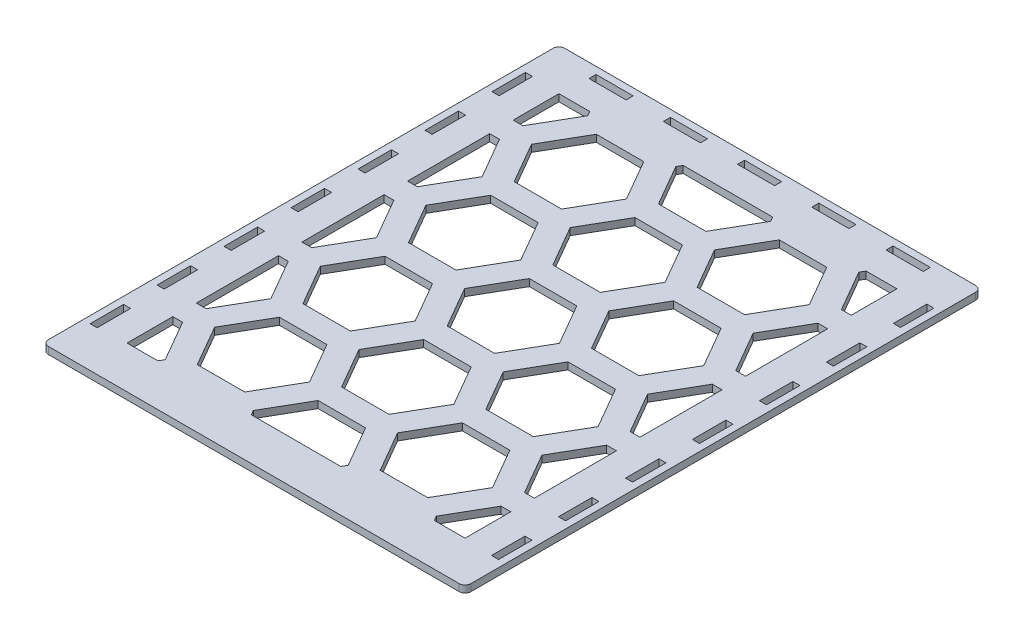
SolidWorks part; units mm, degrees
ref_plane "Front Plane" through (0, 0, 0) normal (0, 0, 1) x (1, 0, 0)
ref_plane "Top Plane" through (0, 0, 0) normal (0, 1, 0) x (1, 0, 0)
ref_plane "Right Plane" through (0, 0, 0) normal (1, 0, 0) x (0, 0, -1)
sketch "Sketch1" plane through (0, 0, 0) normal (0, 1, 0) x (1, 0, 0)
  line L3 (90, 110) -> (90, -110)
  line L6 (90, -110) -> (-90, -110)
  line L9 (-90, -110) -> (-90, 110)
  line L14 (-90, 110) -> (90, 110)
  line L15 (0, 110) -> (0, -110) construction
  point P1 (0, 0)
  point P4 (0, 110)
  point P21 (0, -110)
  dimension "D1" = 180
  dimension "D3" = 220
extrude "Boss-Extrude1" add sketch "Sketch1" along normal blind 3
sketch "Sketch2" plane through (0, 3, 0) normal (0, 1, 0) x (1, 0, 0)
  line L0 (-55.3636, 104) -> (-39.5455, 104) construction
  line L1 (-7.9091, 104) -> (7.9091, 104)
  line L2 (-7.9091, 104) -> (-7.9091, 107)
  line L3 (-7.9091, 107) -> (7.9091, 107)
  line L4 (7.9091, 104) -> (7.9091, 107)
  line L5 (-7.9091, 104) -> (7.9091, 107) construction
  line L6 (-7.9091, 107) -> (7.9091, 104) construction
  line L7 (23.7273, 104) -> (39.5455, 104)
  line L8 (23.7273, 104) -> (23.7273, 107)
  line L9 (23.7273, 107) -> (39.5455, 107)
  line L10 (39.5455, 104) -> (39.5455, 107)
  line L11 (23.7273, 104) -> (39.5455, 107) construction
  line L12 (23.7273, 107) -> (39.5455, 104) construction
  line L13 (55.3636, 104) -> (71.1818, 104)
  line L14 (55.3636, 104) -> (55.3636, 107)
  line L15 (55.3636, 107) -> (71.1818, 107)
  line L16 (87, 107) -> (-87, 107)
  line L17 (-87, 107) -> (-87, -107)
  line L18 (-90, 110) -> (-90, -110) construction
  line L19 (84, -64.2) -> (84, -78.4667) construction
  line L20 (-87, -107) -> (87, -107)
  line L21 (87, -64.2) -> (84, -64.2)
  line L22 (87, -64.2) -> (87, -49.9333)
  line L23 (87, -107) -> (87, 107)
  line L24 (87, 107) -> (-87, 107) construction
  line L32 (71.1818, 104) -> (71.1818, 107)
  line L33 (55.3636, 104) -> (71.1818, 107) construction
  line L34 (55.3636, 107) -> (71.1818, 104) construction
  line L35 (-39.5455, 104) -> (-23.7273, 104)
  line L36 (-39.5455, 104) -> (-39.5455, 107)
  line L37 (-39.5455, 107) -> (-23.7273, 107)
  line L38 (-23.7273, 104) -> (-23.7273, 107)
  line L39 (-39.5455, 104) -> (-23.7273, 107) construction
  line L40 (-39.5455, 107) -> (-23.7273, 104) construction
  line L41 (-71.1818, 104) -> (-55.3636, 104)
  line L42 (-71.1818, 104) -> (-71.1818, 107)
  line L43 (-71.1818, 107) -> (-55.3636, 107)
  line L44 (-55.3636, 104) -> (-55.3636, 107)
  line L45 (-71.1818, 104) -> (-55.3636, 107) construction
  line L46 (-71.1818, 107) -> (-55.3636, 104) construction
  line L47 (-23.7273, 104) -> (-7.9091, 104) construction
  line L48 (7.9091, 104) -> (23.7273, 104) construction
  line L49 (39.5455, 104) -> (55.3636, 104) construction
  line L50 (71.1818, 104) -> (87, 104) construction
  line L51 (-71.1818, 104) -> (-87, 104) construction
  line L52 (87, -49.9333) -> (84, -49.9333)
  line L57 (84, -64.2) -> (84, -49.9333)
  line L58 (87, -64.2) -> (84, -49.9333) construction
  line L63 (87, -49.9333) -> (84, -64.2) construction
  line L64 (87, -92.7333) -> (84, -92.7333)
  line L69 (87, -92.7333) -> (87, -78.4667)
  line L70 (87, -78.4667) -> (84, -78.4667)
  line L75 (84, -92.7333) -> (84, -78.4667)
  line L76 (87, -92.7333) -> (84, -78.4667) construction
  line L81 (87, -78.4667) -> (84, -92.7333) construction
  line L82 (84, -92.7333) -> (84, -107) construction
  line L83 (-90, -110) -> (90, -110) construction
  line L84 (-84, 92.7333) -> (-87, 92.7333)
  line L85 (-87, 78.4667) -> (-87, 92.7333)
  line L86 (-84, 78.4667) -> (-87, 78.4667)
  line L87 (-84, 78.4667) -> (-84, 92.7333)
  line L88 (-84, 64.2) -> (-87, 64.2)
  line L93 (-87, 49.9333) -> (-87, 64.2)
  line L94 (-84, 49.9333) -> (-87, 49.9333)
  line L99 (-84, 49.9333) -> (-84, 64.2)
  line L100 (-84, 35.6667) -> (-87, 35.6667)
  line L105 (-87, 21.4) -> (-87, 35.6667)
  line L106 (-84, 21.4) -> (-87, 21.4)
  line L107 (-84, 21.4) -> (-84, 35.6667)
  line L108 (-84, 7.1333) -> (-87, 7.1333)
  line L109 (-87, -7.1333) -> (-87, 7.1333)
  line L110 (84, 107) -> (84, 92.7333) construction
  line L111 (84, 78.4667) -> (87, 78.4667)
  line L112 (84, 78.4667) -> (84, 92.7333)
  line L113 (84, 92.7333) -> (87, 92.7333)
  line L114 (87, 78.4667) -> (87, 92.7333)
  line L115 (84, 78.4667) -> (87, 92.7333) construction
  line L116 (84, 92.7333) -> (87, 78.4667) construction
  line L117 (84, 49.9333) -> (87, 49.9333)
  line L118 (84, 49.9333) -> (84, 64.2)
  line L119 (84, 64.2) -> (87, 64.2)
  line L120 (87, 49.9333) -> (87, 64.2)
  line L121 (84, 49.9333) -> (87, 64.2) construction
  line L122 (84, 64.2) -> (87, 49.9333) construction
  line L123 (84, 21.4) -> (87, 21.4)
  line L124 (84, 21.4) -> (84, 35.6667)
  line L125 (84, 35.6667) -> (87, 35.6667)
  line L126 (87, 21.4) -> (87, 35.6667)
  line L127 (84, 21.4) -> (87, 35.6667) construction
  line L128 (84, 35.6667) -> (87, 21.4) construction
  line L129 (84, -7.1333) -> (87, -7.1333)
  line L130 (84, -7.1333) -> (84, 7.1333)
  line L131 (84, 7.1333) -> (87, 7.1333)
  line L132 (87, -7.1333) -> (87, 7.1333)
  line L133 (84, -7.1333) -> (87, 7.1333) construction
  line L134 (84, 7.1333) -> (87, -7.1333) construction
  line L135 (84, -35.6667) -> (87, -35.6667)
  line L136 (84, -35.6667) -> (84, -21.4)
  line L137 (84, -21.4) -> (87, -21.4)
  line L138 (87, -35.6667) -> (87, -21.4)
  line L139 (84, -35.6667) -> (87, -21.4) construction
  line L140 (84, -21.4) -> (87, -35.6667) construction
  line L141 (84, 78.4667) -> (84, 64.2) construction
  line L142 (84, 49.9333) -> (84, 35.6667) construction
  line L143 (84, 21.4) -> (84, 7.1333) construction
  line L144 (84, -7.1333) -> (84, -21.4) construction
  line L145 (84, -35.6667) -> (84, -49.9333) construction
  line L146 (-84, -7.1333) -> (-87, -7.1333)
  line L151 (-84, -7.1333) -> (-84, 7.1333)
  line L152 (-84, -21.4) -> (-87, -21.4)
  line L153 (-87, -35.6667) -> (-87, -21.4)
  line L154 (0, -1278.0896) -> (0, 48721.9104) construction
  line L191 (-84, -35.6667) -> (-87, -35.6667)
  line L192 (-84, -35.6667) -> (-84, -21.4)
  line L193 (-87, -49.9333) -> (-84, -49.9333)
  line L194 (-84, -64.2) -> (-84, -49.9333)
  line L195 (-87, -64.2) -> (-84, -64.2)
  line L196 (-87, -64.2) -> (-87, -49.9333)
  line L197 (-87, -78.4667) -> (-84, -78.4667)
  line L198 (-84, -92.7333) -> (-84, -78.4667)
  line L199 (-87, -92.7333) -> (-84, -92.7333)
  line L200 (-87, -92.7333) -> (-87, -78.4667)
  point P0 (0, 105.5)
  point P5 (31.6364, 105.5)
  point P12 (63.2727, 105.5)
  point P18 (85.5, -85.6)
  point P21 (-31.6364, 105.5)
  point P28 (-63.2727, 105.5)
  point P39 (85.5, -57.0667)
  point P78 (85.5, 57.0667)
  point P82 (85.5, 85.6)
  point P89 (85.5, 28.5333)
  point P94 (85.5, 0)
  point P99 (85.5, -28.5333)
  dimension "D2" = 3
  dimension "D3" = 3
  dimension "D4" = 3
  dimension "D5" = 3
  dimension "D1" = 3
extrude "Cut-Extrude1" cut sketch "Sketch2" against normal through all both and the other way through all
fillet "Fillet1" radius 2.5 4 edges at (-90, 1.5, -110) (90, 1.5, -110) (90, 1.5, 110) (-90, 1.5, 110)
sketch "Sketch3" plane through (0, 0, 0) normal (0, 1, 0) x (1, 0, 0)
  line L0 (-145.7809, -27.5) -> (-165.9882, -27.5)
  line L1 (-145.7809, -72.5) -> (-165.9882, -72.5)
  line L2 (-165.9882, -72.5) -> (-176.0918, -90)
  line L3 (-176.0918, -90) -> (-165.9882, -107.5)
  line L4 (-165.9882, -107.5) -> (-145.7809, -107.5)
  line L5 (-145.7809, -107.5) -> (-135.6773, -90)
  line L6 (-135.6773, -90) -> (-145.7809, -72.5)
  line L13 (-165.9882, -27.5) -> (-176.0918, -45)
  line L14 (-137.1207, -112.5) -> (-127.0171, -130)
  line L15 (-127.0171, -130) -> (-106.8098, -130)
  line L16 (-106.8098, -130) -> (-96.7062, -112.5)
  line L17 (-96.7062, -112.5) -> (-106.8098, -95)
  line L18 (-106.8098, -95) -> (-127.0171, -95)
  line L19 (-127.0171, -95) -> (-137.1207, -112.5)
  line L20 (-176.0918, -45) -> (-165.9882, -62.5)
  line L21 (-165.9882, -62.5) -> (-145.7809, -62.5)
  line L22 (-145.7809, -62.5) -> (-135.6773, -45)
  line L23 (-135.6773, -45) -> (-145.7809, -27.5)
  line L24 (-137.1207, -67.5) -> (-127.0171, -85)
  line L25 (-127.0171, -85) -> (-106.8098, -85)
  line L26 (-106.8098, -85) -> (-96.7062, -67.5)
  line L27 (-96.7062, -67.5) -> (-106.8098, -50)
  line L28 (-106.8098, -50) -> (-127.0171, -50)
  line L29 (-127.0171, -50) -> (-137.1207, -67.5)
  line L30 (-145.7809, 17.5) -> (-165.9882, 17.5)
  line L31 (-165.9882, 17.5) -> (-176.0918, 0)
  line L32 (-176.0918, 0) -> (-165.9882, -17.5)
  line L33 (-165.9882, -17.5) -> (-145.7809, -17.5)
  line L34 (-145.7809, -17.5) -> (-135.6773, 0)
  line L35 (-135.6773, 0) -> (-145.7809, 17.5)
  line L36 (-137.1207, -22.5) -> (-127.0171, -40)
  line L37 (-127.0171, -40) -> (-106.8098, -40)
  line L38 (-106.8098, -40) -> (-96.7062, -22.5)
  line L39 (-96.7062, -22.5) -> (-106.8098, -5)
  line L40 (-106.8098, -5) -> (-127.0171, -5)
  line L41 (-127.0171, -5) -> (-137.1207, -22.5)
  line L42 (-145.7809, 62.5) -> (-165.9882, 62.5)
  line L43 (-165.9882, 62.5) -> (-176.0918, 45)
  line L44 (-176.0918, 45) -> (-165.9882, 27.5)
  line L45 (-165.9882, 27.5) -> (-145.7809, 27.5)
  line L46 (-145.7809, 27.5) -> (-135.6773, 45)
  line L47 (-135.6773, 45) -> (-145.7809, 62.5)
  line L48 (-137.1207, 22.5) -> (-127.0171, 5)
  line L49 (-127.0171, 5) -> (-106.8098, 5)
  line L50 (-106.8098, 5) -> (-96.7062, 22.5)
  line L51 (-96.7062, 22.5) -> (-106.8098, 40)
  line L52 (-106.8098, 40) -> (-127.0171, 40)
  line L53 (-127.0171, 40) -> (-137.1207, 22.5)
  line L54 (-145.7809, 107.5) -> (-165.9882, 107.5)
  line L55 (-165.9882, 107.5) -> (-176.0918, 90)
  line L56 (-176.0918, 90) -> (-165.9882, 72.5)
  line L57 (-165.9882, 72.5) -> (-145.7809, 72.5)
  line L58 (-145.7809, 72.5) -> (-135.6773, 90)
  line L59 (-135.6773, 90) -> (-145.7809, 107.5)
  line L60 (-137.1207, 67.5) -> (-127.0171, 50)
  line L61 (-127.0171, 50) -> (-106.8098, 50)
  line L62 (-106.8098, 50) -> (-96.7062, 67.5)
  line L63 (-96.7062, 67.5) -> (-106.8098, 85)
  line L64 (-106.8098, 85) -> (-127.0171, 85)
  line L65 (-127.0171, 85) -> (-137.1207, 67.5)
  line L66 (-145.7809, 152.5) -> (-165.9882, 152.5)
  line L67 (-165.9882, 152.5) -> (-176.0918, 135)
  line L68 (-176.0918, 135) -> (-165.9882, 117.5)
  line L69 (-165.9882, 117.5) -> (-145.7809, 117.5)
  line L70 (-145.7809, 117.5) -> (-135.6773, 135)
  line L71 (-135.6773, 135) -> (-145.7809, 152.5)
  line L72 (-137.1207, 112.5) -> (-127.0171, 95)
  line L73 (-127.0171, 95) -> (-106.8098, 95)
  line L74 (-106.8098, 95) -> (-96.7062, 112.5)
  line L75 (-96.7062, 112.5) -> (-106.8098, 130)
  line L76 (-106.8098, 130) -> (-127.0171, 130)
  line L77 (-127.0171, 130) -> (-137.1207, 112.5)
  line L102 (-145.7809, -72.5) -> (-145.7809, -27.5) construction
  line L103 (-127.0171, -95) -> (-127.0171, -85) construction
  line L104 (-140.7291, -81.25) -> (-132.0689, -76.25) construction
  line L105 (-59.1784, 112.5) -> (-49.0748, 95)
  line L106 (-49.0748, 95) -> (-28.8675, 95)
  line L107 (-28.8675, 95) -> (-18.7639, 112.5)
  line L108 (-18.7639, 112.5) -> (-28.8675, 130)
  line L109 (-28.8675, 130) -> (-49.0748, 130)
  line L110 (-49.0748, 130) -> (-59.1784, 112.5)
  line L111 (-67.8387, 152.5) -> (-88.0459, 152.5)
  line L112 (-88.0459, 152.5) -> (-98.1495, 135)
  line L113 (-98.1495, 135) -> (-88.0459, 117.5)
  line L114 (-88.0459, 117.5) -> (-67.8387, 117.5)
  line L115 (-67.8387, 117.5) -> (-57.735, 135)
  line L116 (-57.735, 135) -> (-67.8387, 152.5)
  line L117 (-67.8387, 107.5) -> (-88.0459, 107.5)
  line L118 (-88.0459, 107.5) -> (-98.1495, 90)
  line L119 (-98.1495, 90) -> (-88.0459, 72.5)
  line L120 (-88.0459, 72.5) -> (-67.8387, 72.5)
  line L121 (-67.8387, 72.5) -> (-57.735, 90)
  line L122 (-57.735, 90) -> (-67.8387, 107.5)
  line L123 (-67.8387, 62.5) -> (-88.0459, 62.5)
  line L124 (-88.0459, 62.5) -> (-98.1495, 45)
  line L125 (-98.1495, 45) -> (-88.0459, 27.5)
  line L126 (-88.0459, 27.5) -> (-67.8387, 27.5)
  line L127 (-67.8387, 27.5) -> (-57.735, 45)
  line L128 (-57.735, 45) -> (-67.8387, 62.5)
  line L129 (-67.8387, 17.5) -> (-88.0459, 17.5)
  line L130 (-88.0459, 17.5) -> (-98.1495, 0)
  line L131 (-98.1495, 0) -> (-88.0459, -17.5)
  line L132 (-88.0459, -17.5) -> (-67.8387, -17.5)
  line L133 (-67.8387, -17.5) -> (-57.735, 0)
  line L134 (-57.735, 0) -> (-67.8387, 17.5)
  line L135 (-59.1784, -22.5) -> (-49.0748, -40)
  line L136 (-49.0748, -40) -> (-28.8675, -40)
  line L137 (-28.8675, -40) -> (-18.7639, -22.5)
  line L138 (-18.7639, -22.5) -> (-28.8675, -5)
  line L139 (-28.8675, -5) -> (-49.0748, -5)
  line L140 (-49.0748, -5) -> (-59.1784, -22.5)
  line L141 (-67.8387, -27.5) -> (-88.0459, -27.5)
  line L142 (-88.0459, -27.5) -> (-98.1495, -45)
  line L143 (-98.1495, -45) -> (-88.0459, -62.5)
  line L144 (-88.0459, -62.5) -> (-67.8387, -62.5)
  line L145 (-67.8387, -62.5) -> (-57.735, -45)
  line L146 (-57.735, -45) -> (-67.8387, -27.5)
  line L147 (-59.1784, -67.5) -> (-49.0748, -85)
  line L148 (-49.0748, -85) -> (-28.8675, -85)
  line L149 (-28.8675, -85) -> (-18.7639, -67.5)
  line L150 (-18.7639, -67.5) -> (-28.8675, -50)
  line L151 (-28.8675, -50) -> (-49.0748, -50)
  line L152 (-49.0748, -50) -> (-59.1784, -67.5)
  line L153 (-67.8387, -72.5) -> (-88.0459, -72.5)
  line L154 (-88.0459, -72.5) -> (-98.1495, -90)
  line L155 (-98.1495, -90) -> (-88.0459, -107.5)
  line L156 (-88.0459, -107.5) -> (-67.8387, -107.5)
  line L157 (-67.8387, -107.5) -> (-57.735, -90)
  line L158 (-57.735, -90) -> (-67.8387, -72.5)
  line L159 (-59.1784, -112.5) -> (-49.0748, -130)
  line L160 (-49.0748, -130) -> (-28.8675, -130)
  line L161 (-28.8675, -130) -> (-18.7639, -112.5)
  line L162 (-18.7639, -112.5) -> (-28.8675, -95)
  line L163 (-28.8675, -95) -> (-49.0748, -95)
  line L164 (-49.0748, -95) -> (-59.1784, -112.5)
  line L165 (-59.1784, 22.5) -> (-49.0748, 5)
  line L166 (-49.0748, 5) -> (-28.8675, 5)
  line L167 (-28.8675, 5) -> (-18.7639, 22.5)
  line L168 (-18.7639, 22.5) -> (-28.8675, 40)
  line L169 (-28.8675, 40) -> (-49.0748, 40)
  line L170 (-49.0748, 40) -> (-59.1784, 22.5)
  line L171 (-59.1784, 67.5) -> (-49.0748, 50)
  line L172 (-49.0748, 50) -> (-28.8675, 50)
  line L173 (-28.8675, 50) -> (-18.7639, 67.5)
  line L174 (-18.7639, 67.5) -> (-28.8675, 85)
  line L175 (-28.8675, 85) -> (-49.0748, 85)
  line L176 (-49.0748, 85) -> (-59.1784, 67.5)
  line L177 (18.7639, 112.5) -> (28.8675, 95)
  line L178 (28.8675, 95) -> (49.0748, 95)
  line L179 (49.0748, 95) -> (59.1784, 112.5)
  line L180 (59.1784, 112.5) -> (49.0748, 130)
  line L181 (49.0748, 130) -> (28.8675, 130)
  line L182 (28.8675, 130) -> (18.7639, 112.5)
  line L183 (10.1036, 152.5) -> (-10.1036, 152.5)
  line L184 (-10.1036, 152.5) -> (-20.2073, 135)
  line L185 (-20.2073, 135) -> (-10.1036, 117.5)
  line L186 (-10.1036, 117.5) -> (10.1036, 117.5)
  line L187 (10.1036, 117.5) -> (20.2073, 135)
  line L188 (20.2073, 135) -> (10.1036, 152.5)
  line L189 (10.1036, 107.5) -> (-10.1036, 107.5)
  line L190 (-10.1036, 107.5) -> (-20.2073, 90)
  line L191 (-20.2073, 90) -> (-10.1036, 72.5)
  line L192 (-10.1036, 72.5) -> (10.1036, 72.5)
  line L193 (10.1036, 72.5) -> (20.2073, 90)
  line L194 (20.2073, 90) -> (10.1036, 107.5)
  line L195 (10.1036, 62.5) -> (-10.1036, 62.5)
  line L196 (-10.1036, 62.5) -> (-20.2073, 45)
  line L197 (-20.2073, 45) -> (-10.1036, 27.5)
  line L198 (-10.1036, 27.5) -> (10.1036, 27.5)
  line L199 (10.1036, 27.5) -> (20.2073, 45)
  line L200 (20.2073, 45) -> (10.1036, 62.5)
  line L201 (10.1036, 17.5) -> (-10.1036, 17.5)
  line L202 (-10.1036, 17.5) -> (-20.2073, 0)
  line L203 (-20.2073, 0) -> (-10.1036, -17.5)
  line L204 (-10.1036, -17.5) -> (10.1036, -17.5)
  line L205 (10.1036, -17.5) -> (20.2073, 0)
  line L206 (20.2073, 0) -> (10.1036, 17.5)
  line L207 (18.7639, -22.5) -> (28.8675, -40)
  line L208 (28.8675, -40) -> (49.0748, -40)
  line L209 (49.0748, -40) -> (59.1784, -22.5)
  line L210 (59.1784, -22.5) -> (49.0748, -5)
  line L211 (49.0748, -5) -> (28.8675, -5)
  line L212 (28.8675, -5) -> (18.7639, -22.5)
  line L213 (10.1036, -27.5) -> (-10.1036, -27.5)
  line L214 (-10.1036, -27.5) -> (-20.2073, -45)
  line L215 (-20.2073, -45) -> (-10.1036, -62.5)
  line L216 (-10.1036, -62.5) -> (10.1036, -62.5)
  line L217 (10.1036, -62.5) -> (20.2073, -45)
  line L218 (20.2073, -45) -> (10.1036, -27.5)
  line L219 (18.7639, -67.5) -> (28.8675, -85)
  line L220 (28.8675, -85) -> (49.0748, -85)
  line L221 (49.0748, -85) -> (59.1784, -67.5)
  line L222 (59.1784, -67.5) -> (49.0748, -50)
  line L223 (49.0748, -50) -> (28.8675, -50)
  line L224 (28.8675, -50) -> (18.7639, -67.5)
  line L225 (10.1036, -72.5) -> (-10.1036, -72.5)
  line L226 (-10.1036, -72.5) -> (-20.2073, -90)
  line L227 (-20.2073, -90) -> (-10.1036, -107.5)
  line L228 (-10.1036, -107.5) -> (10.1036, -107.5)
  line L229 (10.1036, -107.5) -> (20.2073, -90)
  line L230 (20.2073, -90) -> (10.1036, -72.5)
  line L231 (18.7639, -112.5) -> (28.8675, -130)
  line L232 (28.8675, -130) -> (49.0748, -130)
  line L233 (49.0748, -130) -> (59.1784, -112.5)
  line L234 (59.1784, -112.5) -> (49.0748, -95)
  line L235 (49.0748, -95) -> (28.8675, -95)
  line L236 (28.8675, -95) -> (18.7639, -112.5)
  line L237 (18.7639, 22.5) -> (28.8675, 5)
  line L238 (28.8675, 5) -> (49.0748, 5)
  line L239 (49.0748, 5) -> (59.1784, 22.5)
  line L240 (59.1784, 22.5) -> (49.0748, 40)
  line L241 (49.0748, 40) -> (28.8675, 40)
  line L242 (28.8675, 40) -> (18.7639, 22.5)
  line L243 (18.7639, 67.5) -> (28.8675, 50)
  line L244 (28.8675, 50) -> (49.0748, 50)
  line L245 (49.0748, 50) -> (59.1784, 67.5)
  line L246 (59.1784, 67.5) -> (49.0748, 85)
  line L247 (49.0748, 85) -> (28.8675, 85)
  line L248 (28.8675, 85) -> (18.7639, 67.5)
  line L249 (96.7062, 112.5) -> (106.8098, 95)
  line L250 (106.8098, 95) -> (127.0171, 95)
  line L251 (127.0171, 95) -> (137.1207, 112.5)
  line L252 (137.1207, 112.5) -> (127.0171, 130)
  line L253 (127.0171, 130) -> (106.8098, 130)
  line L254 (106.8098, 130) -> (96.7062, 112.5)
  line L255 (88.0459, 152.5) -> (67.8387, 152.5)
  line L256 (67.8387, 152.5) -> (57.735, 135)
  line L257 (57.735, 135) -> (67.8387, 117.5)
  line L258 (67.8387, 117.5) -> (88.0459, 117.5)
  line L259 (88.0459, 117.5) -> (98.1495, 135)
  line L260 (98.1495, 135) -> (88.0459, 152.5)
  line L261 (88.0459, 107.5) -> (67.8387, 107.5)
  line L262 (67.8387, 107.5) -> (57.735, 90)
  line L263 (57.735, 90) -> (67.8387, 72.5)
  line L264 (67.8387, 72.5) -> (88.0459, 72.5)
  line L265 (88.0459, 72.5) -> (98.1495, 90)
  line L266 (98.1495, 90) -> (88.0459, 107.5)
  line L267 (88.0459, 62.5) -> (67.8387, 62.5)
  line L268 (67.8387, 62.5) -> (57.735, 45)
  line L269 (57.735, 45) -> (67.8387, 27.5)
  line L270 (67.8387, 27.5) -> (88.0459, 27.5)
  line L271 (88.0459, 27.5) -> (98.1495, 45)
  line L272 (98.1495, 45) -> (88.0459, 62.5)
  line L273 (88.0459, 17.5) -> (67.8387, 17.5)
  line L274 (67.8387, 17.5) -> (57.735, 0)
  line L275 (57.735, 0) -> (67.8387, -17.5)
  line L276 (67.8387, -17.5) -> (88.0459, -17.5)
  line L277 (88.0459, -17.5) -> (98.1495, 0)
  line L278 (98.1495, 0) -> (88.0459, 17.5)
  line L279 (96.7062, -22.5) -> (106.8098, -40)
  line L280 (106.8098, -40) -> (127.0171, -40)
  line L281 (127.0171, -40) -> (137.1207, -22.5)
  line L282 (137.1207, -22.5) -> (127.0171, -5)
  line L283 (127.0171, -5) -> (106.8098, -5)
  line L284 (106.8098, -5) -> (96.7062, -22.5)
  line L285 (88.0459, -27.5) -> (67.8387, -27.5)
  line L286 (67.8387, -27.5) -> (57.735, -45)
  line L287 (57.735, -45) -> (67.8387, -62.5)
  line L288 (67.8387, -62.5) -> (88.0459, -62.5)
  line L289 (88.0459, -62.5) -> (98.1495, -45)
  line L290 (98.1495, -45) -> (88.0459, -27.5)
  line L291 (96.7062, -67.5) -> (106.8098, -85)
  line L292 (106.8098, -85) -> (127.0171, -85)
  line L293 (127.0171, -85) -> (137.1207, -67.5)
  line L294 (137.1207, -67.5) -> (127.0171, -50)
  line L295 (127.0171, -50) -> (106.8098, -50)
  line L296 (106.8098, -50) -> (96.7062, -67.5)
  line L297 (88.0459, -72.5) -> (67.8387, -72.5)
  line L298 (67.8387, -72.5) -> (57.735, -90)
  line L299 (57.735, -90) -> (67.8387, -107.5)
  line L300 (67.8387, -107.5) -> (88.0459, -107.5)
  line L301 (88.0459, -107.5) -> (98.1495, -90)
  line L302 (98.1495, -90) -> (88.0459, -72.5)
  line L303 (96.7062, -112.5) -> (106.8098, -130)
  line L304 (106.8098, -130) -> (127.0171, -130)
  line L305 (127.0171, -130) -> (137.1207, -112.5)
  line L306 (137.1207, -112.5) -> (127.0171, -95)
  line L307 (127.0171, -95) -> (106.8098, -95)
  line L308 (106.8098, -95) -> (96.7062, -112.5)
  line L309 (96.7062, 22.5) -> (106.8098, 5)
  line L310 (106.8098, 5) -> (127.0171, 5)
  line L311 (127.0171, 5) -> (137.1207, 22.5)
  line L312 (137.1207, 22.5) -> (127.0171, 40)
  line L313 (127.0171, 40) -> (106.8098, 40)
  line L314 (106.8098, 40) -> (96.7062, 22.5)
  line L315 (96.7062, 67.5) -> (106.8098, 50)
  line L316 (106.8098, 50) -> (127.0171, 50)
  line L317 (127.0171, 50) -> (137.1207, 67.5)
  line L318 (137.1207, 67.5) -> (127.0171, 85)
  line L319 (127.0171, 85) -> (106.8098, 85)
  line L320 (106.8098, 85) -> (96.7062, 67.5)
  line L321 (-137.1207, 112.5) -> (-59.1784, 112.5) construction
  line L322 (-93.0977, -81.25) -> (-101.758, -76.25) construction
  line L323 (84, 78.4667) -> (84, 92.7333) construction
  line L328 (-72, -92) -> (72, -92)
  line L329 (-72, -92) -> (-72, 92)
  line L330 (-72, 92) -> (72, 92)
  line L331 (72, -92) -> (72, 92)
  line L332 (-72, -92) -> (72, 92) construction
  line L333 (-72, 92) -> (72, -92) construction
  line L334 (71.1818, 104) -> (55.3636, 104) construction
  circle A0 centre (-155.8846, -90) radius 17.5 construction
  circle A1 centre (-116.9134, -112.5) radius 17.5 construction
  point P10 (-127.0171, -90)
  point P301 (0, -62.5)
  point P302 (0, 0)
  point P311 (72, 0)
  dimension "D3" = 35
  dimension "D2" = 45
  dimension "D5" = 12
  dimension "D6" = 12
  dimension "D1" = 6
  dimension "D4" = 4
extrude "Cut-Extrude3" cut sketch "Sketch3" against normal through all both and the other way through all contours L329 L328 L157 L158 L153 | L151 L152 L147 L148 L149 L150 | L227 L328 L229 L230 L225 L226 | L223 L224 L219 L220 L221 L222 | L328 L331 L297 L298 L299 | L288 L331 L285 L286 L287 | L211 L212 L207 L208 L209 L210 | L139 L140 L135 L136 L137 L138 | L217 L218 L213 L214 L215 L216 | L329 L144 L145 L146 L141 | L329 L132 L133 L134 L129 | L169 L170 L165 L166 L167 L168 | L205 L206 L201 L202 L203 L204 | L241 L242 L237 L238 L239 L240 | L276 L331 L273 L274 L275 | L199 L200 L195 L196 L197 L198 | L175 L176 L171 L172 L173 L174 | L329 L126 L127 L128 L123 | L330 L329 L120 L121 L122 | L330 L190 L191 L192 L193 L194 | L247 L248 L243 L244 L245 L246 | L264 L331 L330 L262 L263 | L270 L331 L267 L268 L269 region at (-66.6734, 0, -84.0303) region at (0, 0, -83.3528) region at (-66.9317, 0, -45) region at (66.6734, 0, -84.0303) region at (-66.9317, 0, 0) region at (66.9317, 0, -45) region at (-66.9317, 0, 45) region at (66.9317, 0, 0) region at (-66.6734, 0, 84.0303) region at (66.9317, 0, 45) region at (0, 0, 83.3528) region at (66.6734, 0, 84.0303) region at (-38.9711, 0, 22.5) region at (-38.9711, 0, 67.5) region at (-38.9711, 0, -22.5) region at (-38.9711, 0, -67.5) region at (0, 0, -45) region at (0, 0, 0) region at (38.9711, 0, 22.5) region at (0, 0, 45) region at (38.9711, 0, 67.5) region at (38.9711, 0, -22.5) region at (38.9711, 0, -67.5)
equation "\"bottomLength\"= 220mm"
equation "\"topLength\"= 330mm"
equation "\"frontHeight\"= 100mm"
equation "\"height\"= 180mm"
equation "\"width\"= 180mm"
equation "\"D3@Sketch1\"=\"bottomLength\""
equation "\"D1@Sketch1\"=\"width\""
